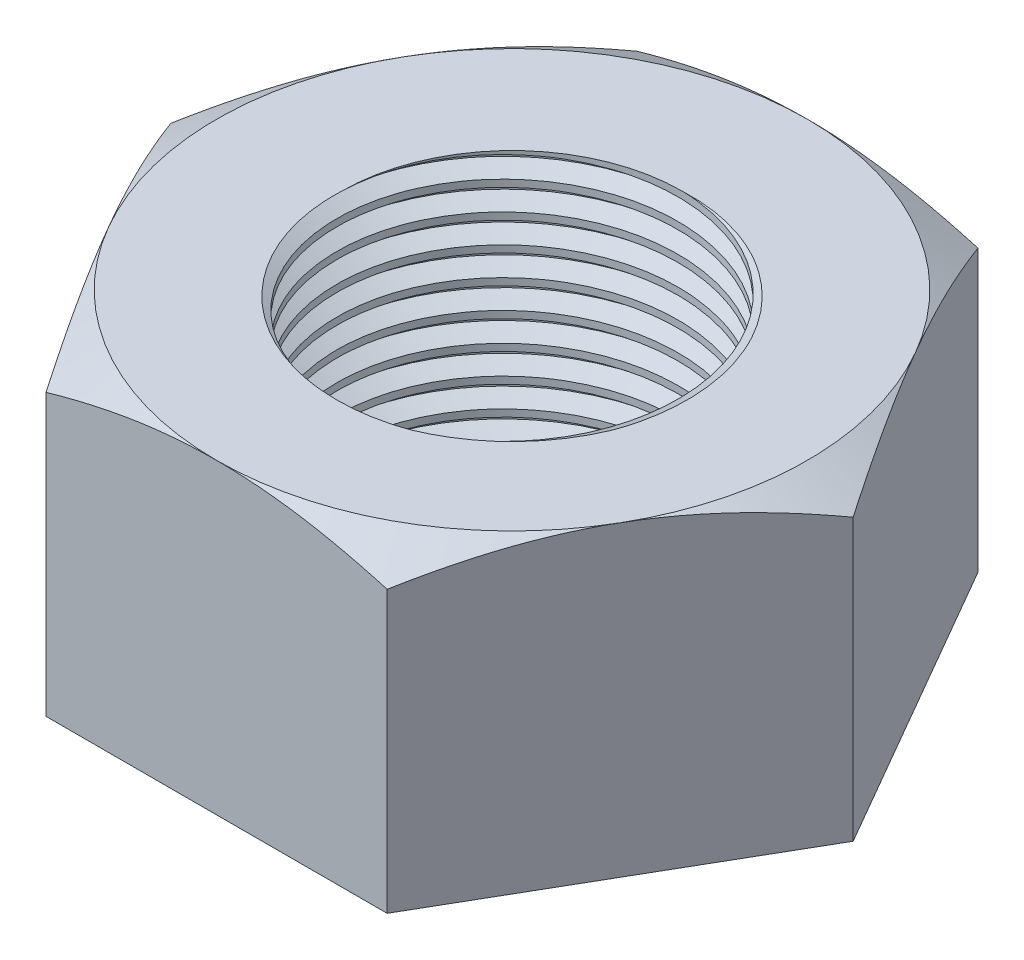
SolidWorks part; units mm, degrees
ref_plane "Front Plane" through (0, 0, 0) normal (0, 0, 1) x (1, 0, 0)
ref_plane "Top Plane" through (0, 0, 0) normal (0, 1, 0) x (1, 0, 0)
ref_plane "Right Plane" through (0, 0, 0) normal (1, 0, 0) x (0, 0, -1)
sketch "Sketch1" plane through (0, 0, 0) normal (0, 1, 0) x (1, 0, 0)
  line L1 (12, -20.7846) -> (24, 0)
  line L2 (24, 0) -> (12, 20.7846)
  line L3 (12, 20.7846) -> (-12, 20.7846)
  line L4 (-12, 20.7846) -> (-24, 0)
  line L5 (-24, 0) -> (-12, -20.7846)
  line L6 (-12, -20.7846) -> (12, -20.7846)
  circle A0 centre (0, 0) radius 20.7846 construction
  dimension "D1" = 48
extrude "Boss-Extrude1" add sketch "Sketch1" along normal blind 21.6
sketch "Sketch2" plane through (0, 0, 0) normal (1, 0, 0) x (0, 0, -1)
  line L0 (20.7846, 21.6) -> (24.2487, 21.6)
  line L1 (24.2487, 21.6) -> (24.2487, 19.6)
  line L2 (24.2487, 19.6) -> (20.7846, 21.6)
  line L3 (0, 0) -> (0, -50000) construction
  dimension "D1" = 30
  dimension "D2" = 2
revolve "Cut-Revolve1" cut sketch "Sketch2" angle 360 about L3
sketch "Sketch5" plane through (0, 21.6, 0) normal (0, 1, 0) x (1, 0, 0)
  circle A0 centre (0, 0) radius 12
  dimension "D1" = 24
extrude "Cut-Extrude1" cut sketch "Sketch5" against normal through all both and the other way through all
thread "Thread1" pitch 2 method cut profile "Thread Profile1" start angle 0, offset 4, length 0, pitch 2, diameter 24
ref_plane "Plane1" through (-12, 25.6, 0) normal (0, 0, 1) x (-1, 0, 0)
sketch "Thread Profile1" plane through (-12, 25.6, 0) normal (0, 0, 1) x (-1, 0, 0)
  line L0 (0, 0) -> (0, 2) construction
  line L1 (0, 0) -> (1.0825, 0.625)
  line L2 (1.0825, 0.625) -> (1.0825, 0.875)
  line L3 (1.0825, 0.875) -> (0, 1.5)
  line L4 (1.0825, 0.75) -> (0, 0.75) construction
  line L11 (0, 0) -> (0, 1.5)
  point P2 (0, 0)
  dimension "Pitch" = 2
  dimension "Profile_Angle" = 60
  dimension "Profile_Land" = 0.25
  dimension "Profile_Height" = 1.0825
